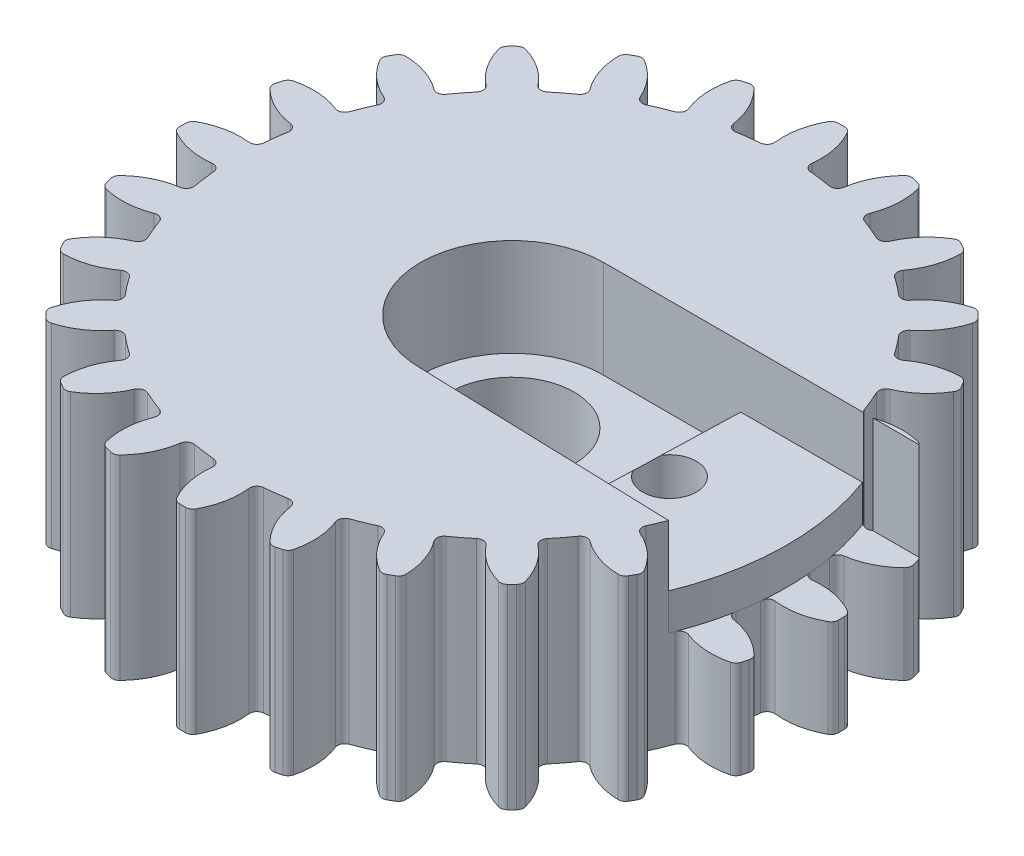
SolidWorks part; units mm, degrees
note: The reader was unsure of these and kept them because the rebuilt part matched: shared geometry of "Sketch2<5>", "Sketch3<2>".
ref_plane "Front Plane" through (0, 0, 0) normal (0, 0, 1) x (1, 0, 0)
ref_plane "Top Plane" through (0, 0, 0) normal (0, 1, 0) x (1, 0, 0)
ref_plane "Right Plane" through (0, 0, 0) normal (1, 0, 0) x (0, 0, -1)
sketch "Sketch2" plane through (0, 0, 0) normal (0, 1, 0) x (1, 0, 0)
  line L0 (0, 0) -> (0, 10.4648) construction
  line L1 (0.3, 13.5) -> (-0.3, 13.5)
  circle A0 centre (0, 0) radius 11.25
  circle A1 centre (0, 0) radius 13.5 construction
  arc A2 (-0.3, 13.5) -> (-0.7, 11.2282) centre (2.2249, 11.8843) ccw
  arc A3 (0.3, 13.5) -> (0.7, 11.2282) centre (-2.2249, 11.8843) cw
  circle A4 centre (0, 0) radius 2.55
  arc A5 (-0.7, 11.2282) -> (0.7, 11.2282) centre (0, 0) cw
  point P10 (0, 13.5)
  dimension "D1" = 22.5
  dimension "D2" = 27
  dimension "D5" = 5.1
  dimension "D3" = 0.6
  dimension "D4" = 0.7
extrude "Boss-Extrude1" add sketch "Sketch2" along normal blind 8
extrude "Boss-Extrude2" add sketch "Sketch2<5>" along normal blind 8 contours A3 L1 A2 A0
sketch "Sketch2<5>" plane through (0, 0, 0) normal (0, 1, 0) x (1, 0, 0) same geometry as "Sketch2"
pattern_circular "CirPattern2" count 24 over 360 about axis through (0, 0, 0) along (0, 1, 0) of "Boss-Extrude2"
fillet "Fillet1" radius 0.3 96 edges at (5.0079, 4, 10.0739) (6.4902, 4, 11.8413) (7.0098, 4, 11.5413) (6.2203, 4, 9.3739) (2.2299, 4, 11.0268) (3.2043, 4, 13.1176) (3.7838, 4, 12.9624) (3.5822, 4, 10.6644) (-0.7, 4, 11.2282) (-0.3, 4, 13.5) (0.3, 4, 13.5) (0.7, 4, 11.2282) (0.7, 4, -11.2282) (-3.5822, 4, 10.6644) (-3.7838, 4, 12.9624) (0.3, 4, -13.5) (-3.2043, 4, 13.1176) (-2.2299, 4, 11.0268) (-0.3, 4, -13.5) (-6.2203, 4, 9.3739) (-7.0098, 4, 11.5413) (-6.4902, 4, 11.8413) (-5.0079, 4, 10.0739) (-0.7, 4, -11.2282) (-8.4345, 4, 7.4446) (-9.7581, 4, 9.3338) (-9.3338, 4, 9.7581) (-7.4446, 4, 8.4345) (-10.0739, 4, 5.0079) (-11.8413, 4, 6.4902) (-11.5413, 4, 7.0098) (-9.3739, 4, 6.2203) (-11.0268, 4, 2.2299) (-13.1176, 4, 3.2043) (-12.9624, 4, 3.7838) (-10.6644, 4, 3.5822) (-11.2282, 4, -0.7) (-13.5, 4, -0.3) (-13.5, 4, 0.3) (-11.2282, 4, 0.7) (-10.6644, 4, -3.5822) (-12.9624, 4, -3.7838) (-13.1176, 4, -3.2043) (-11.0268, 4, -2.2299) (-9.3739, 4, -6.2203) (-11.5413, 4, -7.0098) (-11.8413, 4, -6.4902) (-10.0739, 4, -5.0079) (-7.4446, 4, -8.4345) (-9.3338, 4, -9.7581) (-9.7581, 4, -9.3338) (-8.4345, 4, -7.4446) (-5.0079, 4, -10.0739) (-6.4902, 4, -11.8413) (-7.0098, 4, -11.5413) (-6.2203, 4, -9.3739) (11.2282, 4, 0.7) (13.5, 4, 0.3) (13.5, 4, -0.3) (11.2282, 4, -0.7) (11.0268, 4, -2.2299) (13.1176, 4, -3.2043) (12.9624, 4, -3.7838) (10.6644, 4, -3.5822) (10.0739, 4, -5.0079) (11.8413, 4, -6.4902) (11.5413, 4, -7.0098) (9.3739, 4, -6.2203) (8.4345, 4, -7.4446) (9.7581, 4, -9.3338) (9.3338, 4, -9.7581) (7.4446, 4, -8.4345) (6.2203, 4, -9.3739) (7.0098, 4, -11.5413) (6.4902, 4, -11.8413) (5.0079, 4, -10.0739) (3.5822, 4, -10.6644) (3.7838, 4, -12.9624) (3.2043, 4, -13.1176) (2.2299, 4, -11.0268) (-2.2299, 4, -11.0268) (-3.2043, 4, -13.1176) (-3.7838, 4, -12.9624) (-3.5822, 4, -10.6644) (10.6644, 4, 3.5822) (12.9624, 4, 3.7838) (13.1176, 4, 3.2043) (11.0268, 4, 2.2299) (9.3739, 4, 6.2203) (11.5413, 4, 7.0098) (11.8413, 4, 6.4902) (10.0739, 4, 5.0079) (7.4446, 4, 8.4345) (9.3338, 4, 9.7581) (9.7581, 4, 9.3338) (8.4345, 4, 7.4446)
sketch "Sketch3" plane through (0, 8, 0) normal (0, 1, 0) x (1, 0, 0)
  line L0 (0, 0) -> (6.45, 0) construction
  circle A0 centre (6.45, 0) radius 1.1
  dimension "D1" = 2.2
  dimension "D2" = 6.45
extrude "Cut-Extrude1" cut sketch "Sketch3" against normal blind 10
sketch "Sketch4" plane through (0, 8, 0) normal (0, 1, 0) x (1, 0, 0)
  line L0 (0, 0) -> (6.4987, 0) construction
  line L1 (0, 3.75) -> (16.2485, 3.75)
  line L2 (16.2485, 3.75) -> (16.2485, -4.25)
  line L3 (16.2485, -4.25) -> (0, -3.75)
  arc A0 (0, 3.75) -> (0, -3.75) centre (0, 0) ccw
  dimension "D1" = 7.5
  dimension "D2" = 8
extrude "Cut-Extrude2" cut sketch "Sketch4" against normal blind 4
sketch "Sketch5" plane through (0, 4, 0) normal (0, 1, 0) x (1, 0, 0)
  line L0 (10.5568, 3.888) -> (4.1206, 3.75)
  line L1 (10.6605, 3.75) -> (0, 3.75) construction
  line L2 (4.1206, 3.75) -> (3.8861, -3.8696)
  line L3 (0, -3.75) -> (10.4869, -4.0727) construction
  line L4 (3.8861, -3.8696) -> (10.4869, -4.0727)
  arc A0 (10.5568, 3.888) -> (10.4869, -4.0727) centre (0.5364, -0.0047) cw
extrude "Boss-Extrude3" add sketch "Sketch5" along normal blind 1.5
chamfer "Chamfer1" distance 1.5 angle 45 1 edges at (4.0033, 5.5, 0.0598)
extrude "Cut-Extrude3" cut sketch "Sketch3<2>" against normal blind 10
sketch "Sketch3<2>" plane through (0, 8, 0) normal (0, 1, 0) x (1, 0, 0) same geometry as "Sketch3"
